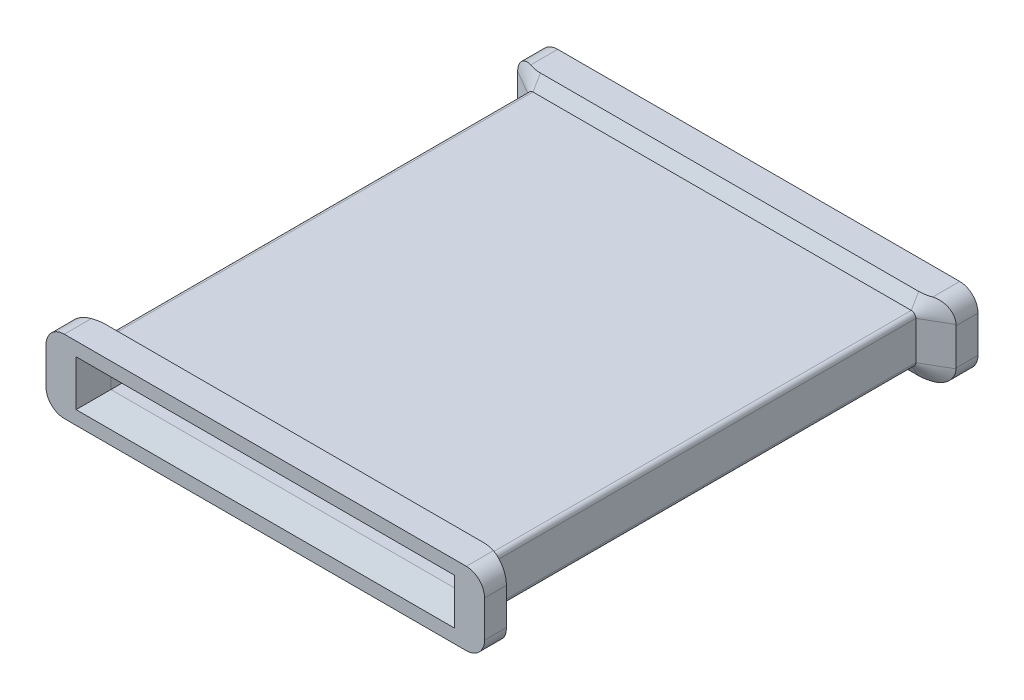
SolidWorks part; units mm, degrees
material "ABS"
ref_plane "Front Plane" through (0, 0, 0) normal (0, 0, 1) x (1, 0, 0)
ref_plane "Top Plane" through (0, 0, 0) normal (0, 1, 0) x (1, 0, 0)
ref_plane "Right Plane" through (0, 0, 0) normal (1, 0, 0) x (0, 0, -1)
sketch "Sketch1" plane through (0, 0, 0) normal (0, 0, 1) x (1, 0, 0)
  line L0 (0, 8) -> (48, 8)
  line L3 (48, 8) -> (48, 0)
  line L4 (48, 0) -> (0, 0)
  line L5 (0, 0) -> (0, 8)
  line L9 (3.6, 6.2) -> (44.4, 6.2)
  line L10 (3.6, 6.2) -> (3.6, 1.8)
  line L11 (3.6, 1.8) -> (44.4, 1.8)
  line L12 (44.4, 6.2) -> (44.4, 1.8)
  dimension "D1" = 1.8
  dimension "D2" = 40.8
  dimension "D4" = 4.4
  dimension "D5" = 1.8
  dimension "D7" = 3.6
  dimension "D8" = 3.6
extrude "Boss-Extrude1" add sketch "Sketch1" along normal blind 54
sketch "Sketch2" plane through (0, 0, 54) normal (0, 0, 1) x (1, 0, 0)
  line L1 (3.3, 6.6) -> (44.7, 6.6)
  line L2 (2.8, 6.1) -> (2.8, 1.9)
  line L3 (3.3, 1.4) -> (44.7, 1.4)
  line L4 (45.2, 6.1) -> (45.2, 1.9)
  line L5 (3.6, 1.8) -> (44.4, 1.8) construction
  line L6 (44.4, 6.2) -> (3.6, 6.2) construction
  line L8 (3.6, 6.2) -> (3.6, 1.8) construction
  line L9 (44.4, 1.8) -> (44.4, 6.2) construction
  arc A0 (2.8, 1.9) -> (3.3, 1.4) centre (3.3, 1.9) ccw
  arc A1 (44.7, 1.4) -> (45.2, 1.9) centre (44.7, 1.9) ccw
  arc A2 (44.7, 6.6) -> (45.2, 6.1) centre (44.7, 6.1) cw
  arc A3 (3.3, 6.6) -> (2.8, 6.1) centre (3.3, 6.1) ccw
  dimension "D1" = 0.5
  dimension "D2" = 0.4
  dimension "D3" = 0.8
  dimension "D4" = 0.8
  dimension "D5" = 0.4
extrude "Cut-Extrude1" cut sketch "Sketch2" against normal offset from surface (50 mm away) 2 from offset 2 flip side to cut up to face at (24, 4, 0) offset against normal yes
fillet "Fillet1" radius 2 8 edges at (48, 8, 53) (48, 0, 53) (48, 0, 1) (48, 8, 1) (0, 0, 1) (0, 8, 1) (0, 0, 53) (0, 8, 53)
chamfer "Chamfer4" distance 2 angle 60 16 edges at (2.8, 4, 52) (2.9464, 1.5464, 52) (2.9464, 6.4536, 52) (24, 1.4, 52) (24, 6.6, 52) (45.0536, 1.5464, 52) (45.0536, 6.4536, 52) (45.2, 4, 52) (2.8, 4, 2) (2.9464, 1.5464, 2) (2.9464, 6.4536, 2) (24, 1.4, 2) (24, 6.6, 2) (45.0536, 1.5464, 2) (45.0536, 6.4536, 2) (45.2, 4, 2) first distance on face at (2.8, 4, 27) first distance on face at (2.9982, 1.5982, 27) first distance on face at (2.9982, 6.4018, 27) first distance on face at (24, 1.4, 27) first distance on face at (24, 6.6, 27) first distance on face at (45.0018, 1.5982, 27) first distance on face at (45.0018, 6.4018, 27) first distance on face at (45.2, 4, 27)
chamfer "Chamfer5" distance 3.5 angle 5 8 edges at (44.4, 4, 54) (24, 1.8, 54) (3.6, 4, 54) (24, 6.2, 54) (44.4, 4, 0) (24, 1.8, 0) (3.6, 4, 0) (24, 6.2, 0) first distance on face at (44.4, 4, 27) first distance on face at (24, 1.8, 27) first distance on face at (3.6, 4, 27) first distance on face at (24, 6.2, 27)
